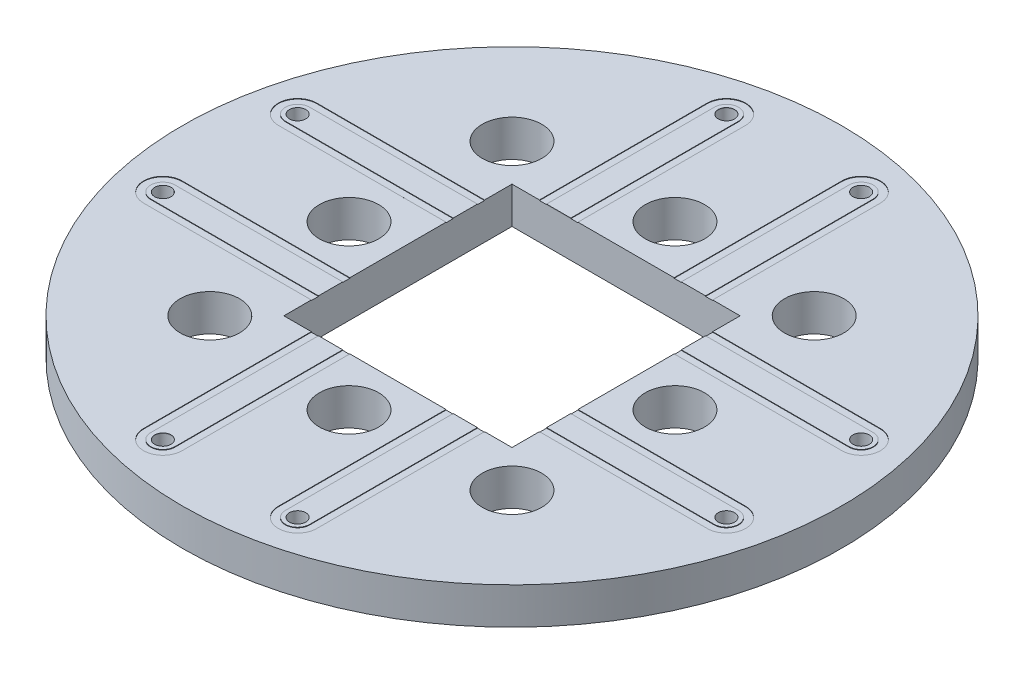
SolidWorks part; units mm, degrees
material "Ceramic Porcelain"
ref_plane "Front Plane" through (0, 0, 0) normal (0, 0, 1) x (1, 0, 0)
ref_plane "Top Plane" through (0, 0, 0) normal (0, 1, 0) x (1, 0, 0)
ref_plane "Right Plane" through (0, 0, 0) normal (1, 0, 0) x (0, 0, -1)
ref_axis "Y Axis" through (0, 0.0762, 0) along (0, -1, 0)
sketch "Body Sketch" plane through (0, 0, 0) normal (0, 1, 0) x (1, 0, 0)
  circle A0 centre (0, 0) radius 11.557
  dimension "D1" = 23.114
extrude "Body" add sketch "Body Sketch" against normal blind 1.27
sketch "Copper Sketch" plane through (0, 0, 0) normal (0, 1, 0) x (1, 0, 0)
  circle A0 centre (0, 0) radius 11.557
  dimension "D1" = 23.114
extrude "Copper" add sketch "Copper Sketch" along normal blind 0.0175
sketch "IO Hole Positions" plane through (0, 0, 0) normal (0, 1, 0) x (1, 0, 0)
  line L0 (-11.557, 0) -> (11.557, 0) construction
  circle A1 centre (0, 0) radius 11.557 construction
  point P1 (-2.3622, 9.8816)
  point P8 (-2.3622, -9.8816)
  dimension "D2" = 2.3622
sketch "Gap" plane through (0, 0, 0) normal (0, 1, 0) x (1, 0, 0)
  line L10 (-3.0372, 9.8816) -> (-3.0372, -9.8816)
  line L11 (-11.557, 0) -> (11.557, 0) construction
  line L12 (-3.0372, 0) -> (-1.6872, 0) construction
  line L13 (-1.6872, -9.8816) -> (-1.6872, 9.8816)
  arc A5 (-1.6872, 9.8816) -> (-3.0372, 9.8816) centre (-2.3622, 9.8816) ccw
  arc A6 (-1.6872, -9.8816) -> (-3.0372, -9.8816) centre (-2.3622, -9.8816) cw
  dimension "D1" = 0.675
sketch "Center Sketch" plane through (0, 0, 0) normal (0, 1, 0) x (1, 0, 0)
  line L6 (-2.7872, 9.8816) -> (-2.7872, -9.8816)
  line L7 (-11.557, 0) -> (11.557, 0) construction
  line L8 (-2.7872, 0) -> (-1.9372, 0) construction
  line L9 (-1.9372, -9.8816) -> (-1.9372, 9.8816)
  arc A3 (-1.9372, 9.8816) -> (-2.7872, 9.8816) centre (-2.3622, 9.8816) ccw
  arc A4 (-1.9372, -9.8816) -> (-2.7872, -9.8816) centre (-2.3622, -9.8816) cw
  dimension "D1" = 0.425
extrude "Gap Cut" cut sketch "Gap" along normal through all
extrude "Center" add sketch "Center Sketch" along normal blind 0.0175 separate body
sketch "IO Hole Sketch" plane through (0, 0, 0) normal (0, 1, 0) x (1, 0, 0)
  circle A1 centre (-2.3622, 9.8816) radius 0.287
  circle A3 centre (-2.3622, -9.8816) radius 0.287
  circle A4 centre (0, 0) radius 10.16 construction
  dimension "D1" = 0.574
  dimension "D2" = 0.574
  dimension "D3" = 20.32
  dimension "D4" = 2.3622
extrude "IO Hole" cut sketch "IO Hole Sketch" against normal through all and the other way through all
pattern_circular "Gap Cuts" count 4 over 360 about axis through (0, 0.0762, 0) along (0, -1, 0) of "Gap Cut"
pattern_circular "Centers" count 4 over 360 about axis through (0, 0.0762, 0) along (0, -1, 0) of "Center"
pattern_circular "IO Holes" count 4 over 360 about axis through (0, 0.0762, 0) along (0, -1, 0) of "IO Hole"
sketch "Pocket Sketch" plane through (0, 0, 0) normal (0, 1, 0) x (1, 0, 0)
  line L1 (-4, -4) -> (4, -4)
  line L2 (-4, -4) -> (-4, 4)
  line L3 (-4, 4) -> (4, 4)
  line L4 (4, -4) -> (4, 4)
  line L5 (-4, -4) -> (4, 4) construction
  line L6 (-4, 4) -> (4, -4) construction
  point P0 (0, 0)
  dimension "D1" = 8
  dimension "D2" = 8
extrude "Pocket" cut sketch "Pocket Sketch" against normal through all and the other way through all
sketch "Posts" plane through (0, 0, 0) normal (0, 1, 0) x (1, 0, 0)
  circle A0 centre (0, 5.715) radius 1.0414
  circle A8 centre (-5.2984, 5.2984) radius 1.0414
  point P0 (0, 5.715)
  point P4 (-5.2984, 5.2984)
  dimension "D2" = 2.0828
  dimension "D4" = 2.0828
  dimension "D1" = 5.715
  dimension "D3" = 7.493
  dimension "D5" = 5.715
extrude "Post Cut" cut sketch "Posts" against normal through all and the other way through all
pattern_circular "Post Cuts" count 4 over 360 about axis through (0, 0.0762, 0) along (0, -1, 0) of "Post Cut"
equation "\"dielectric_d\"= 0.91in"
equation "\"dieletric_h\"= 0.05in"
equation "\"D1@Body\" = \"dieletric_h\""
equation "\"screw_inner_r\"= 0.415in"
equation "\"io_r\"= 0.4in"
equation "\"io_hole_d\"= 0.574mm"
equation "\"W\"= 0.85mm"
equation "\"G\"= 0.25mm"
equation "\"copper_t\"= 17.5um"
equation "\"silicon_size\"= 8mm"
equation "\"D1@Center\" = \"copper_t\""
equation "\"D1@Copper\"=\"copper_t\""
equation "\"D1@Pocket Sketch\" = \"silicon_size\""
equation "\"D2@Pocket Sketch\" = \"silicon_size\""
equation "\"post_r1\"= 0.225in"
equation "\"post_r2\"= 0.295in"
equation "\"D1@Posts\"=\"post_r1\""
equation "\"post_hole_size\"= 0.082in"
equation "\"D2@Posts\"=\"post_hole_size\""
equation "\"D3@Posts\"=\"post_r2\""
equation "\"D4@Posts\"=\"post_hole_size\""
equation "\"io_x\"= 0.093in"
equation "\"D1@IO Hole Positions\"=\"io_r\""
equation "\"D2@IO Hole Positions\"=\"io_x\""
equation "\"D1@IO Hole Sketch\"=\"io_hole_d\""
equation "\"D2@IO Hole Sketch\"=\"io_hole_d\""
equation "\"D1@Gap\"= \"W\" / 2 + \"G\""
equation "\"D1@Center Sketch\"=\"W\" / 2"
equation "\"D5@Posts\"=\"post_r1\""
equation "\"D4@IO Hole Sketch\"=\"io_x\""
equation "\"D1@Body Sketch\"=\"dielectric_d\""
equation "\"D1@Boday Sketch\" = \"dielectric_d\""
